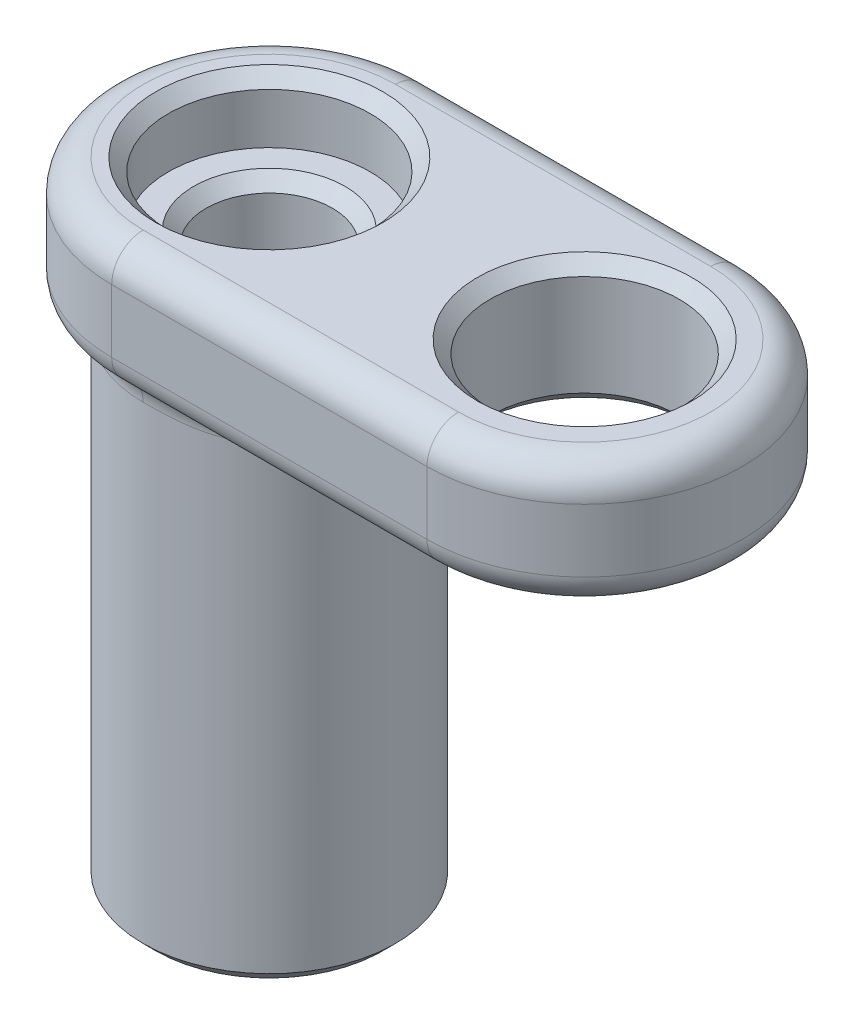
SolidWorks part; units mm, degrees
ref_plane "Front Plane" through (0, 0, 0) normal (0, 0, 1) x (1, 0, 0)
ref_plane "Top Plane" through (0, 0, 0) normal (0, 1, 0) x (1, 0, 0)
ref_plane "Right Plane" through (0, 0, 0) normal (1, 0, 0) x (0, 0, -1)
sketch "Sketch1" plane through (0, 0, 0) normal (0, 1, 0) x (1, 0, 0)
  circle A0 centre (0, 0) radius 20
  dimension "D1" = 40
extrude "Boss-Extrude1" add sketch "Sketch1" along normal blind 100
sketch "Sketch2" plane through (0, 100, 0) normal (0, 1, 0) x (1, 0, 0)
  line L0 (0, 0) -> (50, 0) construction
  line L1 (0, 25) -> (50, 25)
  line L2 (0, -25) -> (50, -25)
  arc A0 (0, 25) -> (0, -25) centre (0, 0) ccw
  arc A1 (50, -25) -> (50, 25) centre (50, 0) ccw
  point P3 (25, 0)
  dimension "D2" = 25
  dimension "D1" = 50
extrude "Boss-Extrude2" add sketch "Sketch2" against normal blind 20
hole_wizard "CBORE for M5 Hex Head Bolt1" positions "Sketch3" profile "Sketch5" counterbore size "M5" standard "ISO" end condition through all
sketch "Sketch3" plane through (0, 100, 0) normal (0, 1, 0) x (1, 0, 0)
  point P0 (0, 0)
sketch "Sketch5" plane through (0, 100, 0) normal (1, 0, 0) x (0, 0, 1)
  line L0 (0, 0) -> (0, 100)
  line L1 (0, 100) -> (10, 100)
  line L3 (10, 100) -> (10, 10)
  line L4 (10, 10) -> (16, 10)
  line L5 (16, 10) -> (16, 0)
  line L7 (16, 0) -> (0, 0)
  line L11 (0, -6.35) -> (0, 107.95) construction
  dimension "Thru Hole Dia." = 20
  dimension "Thru Hole Depth" = 100
  dimension "C'Bore Dia." = 32
  dimension "C'Bore Depth" = 10
hole_wizard "Ø1.0mm Dowel Hole1" positions "Sketch6" profile "Sketch7" hole size "Ø1.0" standard "ISO" end condition through all
sketch "Sketch6" plane through (0, 100, 0) normal (0, 1, 0) x (1, 0, 0)
  point P0 (50, 0)
sketch "Sketch7" plane through (50, 100, 0) normal (1, 0, 0) x (0, 0, 1)
  line L0 (0, 0) -> (0, 100)
  line L1 (0, 100) -> (15, 100)
  line L2 (15, 100) -> (15, 0)
  line L5 (15, 0) -> (0, 0)
  line L11 (0, -6.35) -> (0, 107.95) construction
  dimension "Thru Hole Dia." = 30
  dimension "Thru Hole Depth" = 100
chamfer "Chamfer1" distance 2 angle 45 5 edges at (0, 90, 10) (0, 0, 10) (50, 80, 15) (0, 100, 16) (50, 100, 15)
fillet "Fillet1" radius 5 8 edges at (25, 80, 25) (-25, 80, 0) (25, 80, -25) (25, 100, 25) (-25, 100, 0) (25, 100, -25) (75, 80, 0) (75, 100, 0)
fillet "Fillet2" radius 5 2 edges at (-20, 80, 0) (20, 80, 0)
chamfer "Chamfer2" distance 2 angle 45 1 edges at (0, 0, 20)
